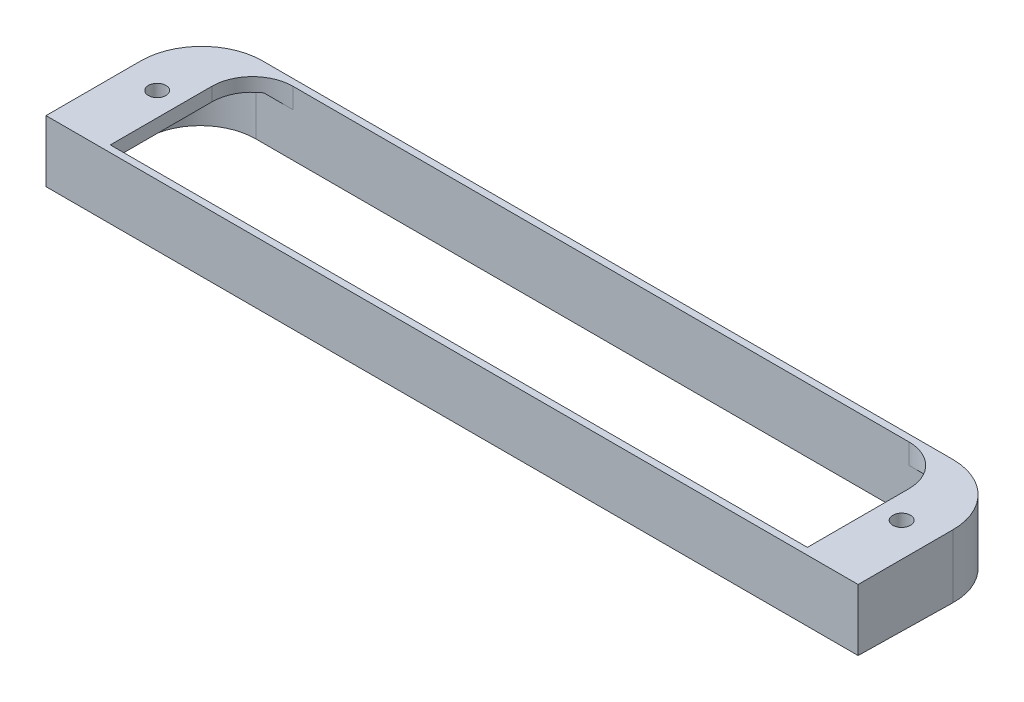
SolidWorks part; units mm, degrees
material "ABS"
ref_plane "Front" through (0, 0, 0) normal (0, 0, 1) x (1, 0, 0)
ref_plane "Top" through (0, 0, 0) normal (0, 1, 0) x (1, 0, 0)
ref_plane "Right" through (0, 0, 0) normal (1, 0, 0) x (0, 0, -1)
ref_axis "X" through (-80.9, 0, 0) along (1, 0, 0)
ref_axis "Y" through (0, -50, 0) along (0, 1, 0)
ref_axis "Z" through (0, 0, -80.9) along (0, 0, 1)
sketch "Sketch1" plane through (0, 0, 0) normal (0, 1, 0) x (1, 0, 0)
  line L0 (-60, 0) -> (-51.5, 0)
  line L1 (-51.5, 1) -> (-51.5, 16)
  line L2 (-45.5, 22) -> (45.5, 22)
  line L3 (51.5, 16) -> (51.5, 1)
  line L4 (51.5, 0) -> (60, 0)
  line L5 (60, 0) -> (60, 14)
  line L6 (51, 23) -> (-51, 23)
  line L7 (-60, 14) -> (-60, 0)
  line L8 (-51.5, 0) -> (51.5, 0)
  line L9 (-51.5, 1) -> (51.5, 1)
  line L10 (-51.5, 0) -> (-51.5, 1) construction
  line L11 (51.5, 0) -> (51.5, 1) construction
  arc A0 (-51.5, 16) -> (-45.5, 22) centre (-45.5, 16) cw
  arc A1 (45.5, 22) -> (51.5, 16) centre (45.5, 16) cw
  arc A2 (60, 14) -> (51, 23) centre (51, 14) ccw
  arc A3 (-51, 23) -> (-60, 14) centre (-51, 14) ccw
  dimension "D5" = 9
  dimension "D6" = 6
  dimension "D1" = 120
  dimension "D2" = 8.5
  dimension "D3" = 1
  dimension "D4" = 23
  dimension "D7" = 1
extrude "Boss-Extrude1" add sketch "Sketch1" along normal blind 2
hole_wizard "M2 Clearance Hole1" positions "Sketch6" profile "Sketch7" hole size "M2" standard "ANSI Metric" end condition up to next
sketch "Sketch6" plane through (0, 2, 0) normal (0, 1, 0) x (1, 0, 0)
  line L0 (-55, 11.43) -> (55, 11.43) construction
  line L3 (0, 11.43) -> (0, 0) construction
  point P0 (-55, 11.43)
  point P2 (55, 11.43)
  dimension "D1" = 11.43
  dimension "D2" = 110
sketch "Sketch7" plane through (-55, 2, -11.43) normal (1, 0, 0) x (0, 0, 1)
  line L0 (0, 0) -> (0, 2)
  line L1 (0, 2) -> (1.3, 2)
  line L2 (1.3, 2) -> (1.3, 0)
  line L5 (1.3, 0) -> (0, 0)
  line L11 (0, -6.35) -> (0, 107.95) construction
  dimension "Thru Hole Dia." = 2.6
  dimension "Thru Hole Depth" = 2
sketch "Sketch8" plane through (0, 0, 0) normal (0, -1, 0) x (-1, 0, 0)
  line L0 (-59, 1) -> (59, 1)
  line L1 (59, 1) -> (59, 14)
  line L2 (51, 22) -> (-51, 22)
  line L3 (-59, 14) -> (-59, 1)
  line L4 (60, 0) -> (60, 14)
  line L5 (51, 23) -> (-51, 23)
  line L6 (-60, 14) -> (-60, 0)
  line L7 (-60, 0) -> (60, 0)
  line L8 (60, 0) -> (60, 14)
  line L9 (51, 23) -> (-51, 23)
  line L10 (-60, 14) -> (-60, 0)
  line L11 (-60, 0) -> (60, 0)
  arc A0 (59, 14) -> (51, 22) centre (51, 14) ccw
  arc A1 (-51, 22) -> (-59, 14) centre (-51, 14) ccw
  arc A2 (60, 14) -> (51, 23) centre (51, 14) ccw
  arc A3 (-51, 23) -> (-60, 14) centre (-51, 14) ccw
  arc A4 (60, 14) -> (51, 23) centre (51, 14) ccw
  arc A5 (-51, 23) -> (-60, 14) centre (-51, 14) ccw
  dimension "D1" = 0
  dimension "D2" = 1
extrude "Boss-Extrude2" add sketch "Sketch8" along normal blind 7.5
chamfer "Chamfer1" distance 1 angle 45 8 edges at (59, 0, -7.5) (48.25, 0, -22) (56.6569, 0, -19.6569) (-59, 0, -7.5) (-56.6569, 0, -19.6569) (-48.25, 0, -22) (55.25, 0, -1) (-55.25, 0, -1)
sketch "Sketch9" plane through (0, 0, 0) normal (1, 0, 0) x (0, 0, -1)
  line L0 (-2, -7.5) -> (23, -7.5)
  line L1 (23, -7.5) -> (-2, -7.0636)
  line L3 (-2, -7.0636) -> (-2, -7.5)
  dimension "D1" = 25
  dimension "D2" = 1
extrude "Cut-Extrude1" cut sketch "Sketch9" against normal through all both and the other way through all
